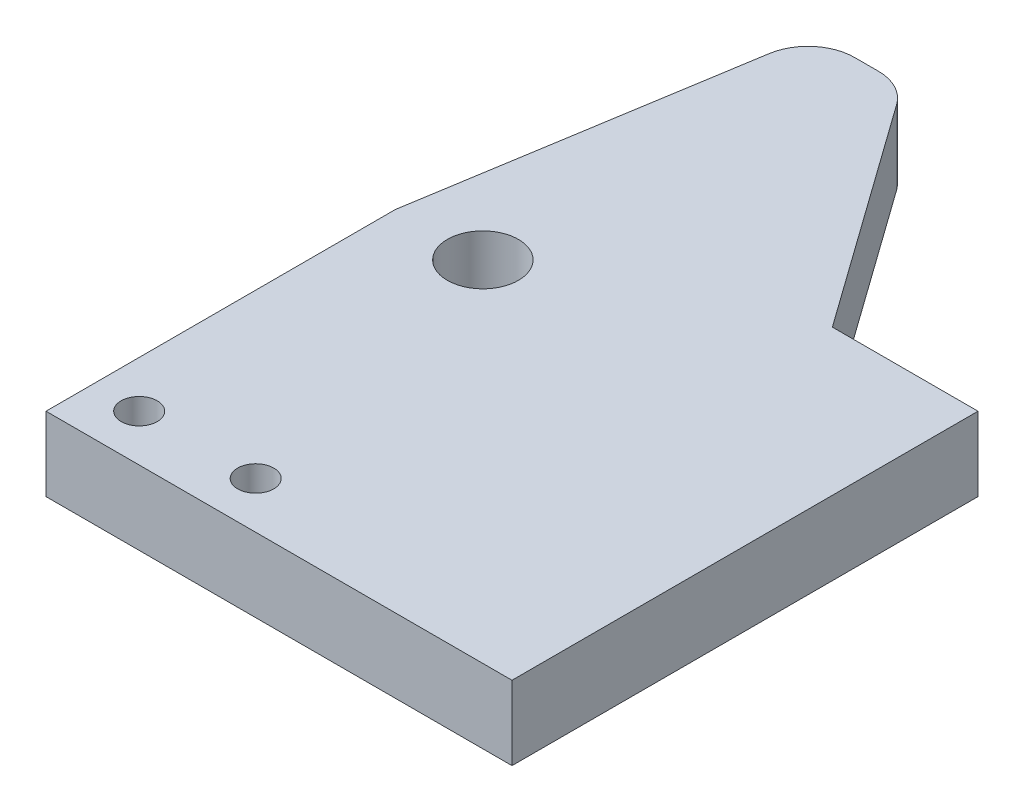
SolidWorks part; units mm, degrees
ref_plane "Front Plane" through (0, 0, 0) normal (0, 0, 1) x (1, 0, 0)
ref_plane "Top Plane" through (0, 0, 0) normal (0, 1, 0) x (1, 0, 0)
ref_plane "Right Plane" through (0, 0, 0) normal (1, 0, 0) x (0, 0, -1)
sketch "Sketch1" plane through (0, 0, 0) normal (0, 1, 0) x (1, 0, 0)
  line L0 (0, 0) -> (-80, 0)
  line L1 (-80, 0) -> (-80, 60)
  line L2 (-80, 60) -> (-71.0849, 115.2739)
  line L3 (-63.1869, 122) -> (-59.1169, 122)
  line L4 (-52.6071, 118.6499) -> (-25, 80)
  line L5 (-25, 80) -> (0, 80)
  line L6 (0, 80) -> (0, 0)
  circle A0 centre (-65, 60) radius 6.1
  arc A1 (-52.6071, 118.6499) -> (-59.1169, 122) centre (-59.1169, 114) ccw
  arc A2 (-71.0849, 115.2739) -> (-63.1869, 122) centre (-63.1869, 114) cw
  circle A3 centre (-72, 8) radius 3.1
  circle A4 centre (-52, 8) radius 3.1
  point P12 (-55, 122)
  point P15 (-70, 122)
  dimension "D8" = 12.2
  dimension "D11" = 8
  dimension "D12" = 6.2
  dimension "D16" = 6.2
  dimension "D1" = 80
  dimension "D2" = 80
  dimension "D3" = 60
  dimension "D4" = 10
  dimension "D5" = 62
  dimension "D6" = 15
  dimension "D7" = 30
  dimension "D9" = 15
  dimension "D10" = 60
  dimension "D13" = 8
  dimension "D14" = 8
  dimension "D15" = 20
extrude "Boss-Extrude1" add sketch "Sketch1" along normal blind 12.7
